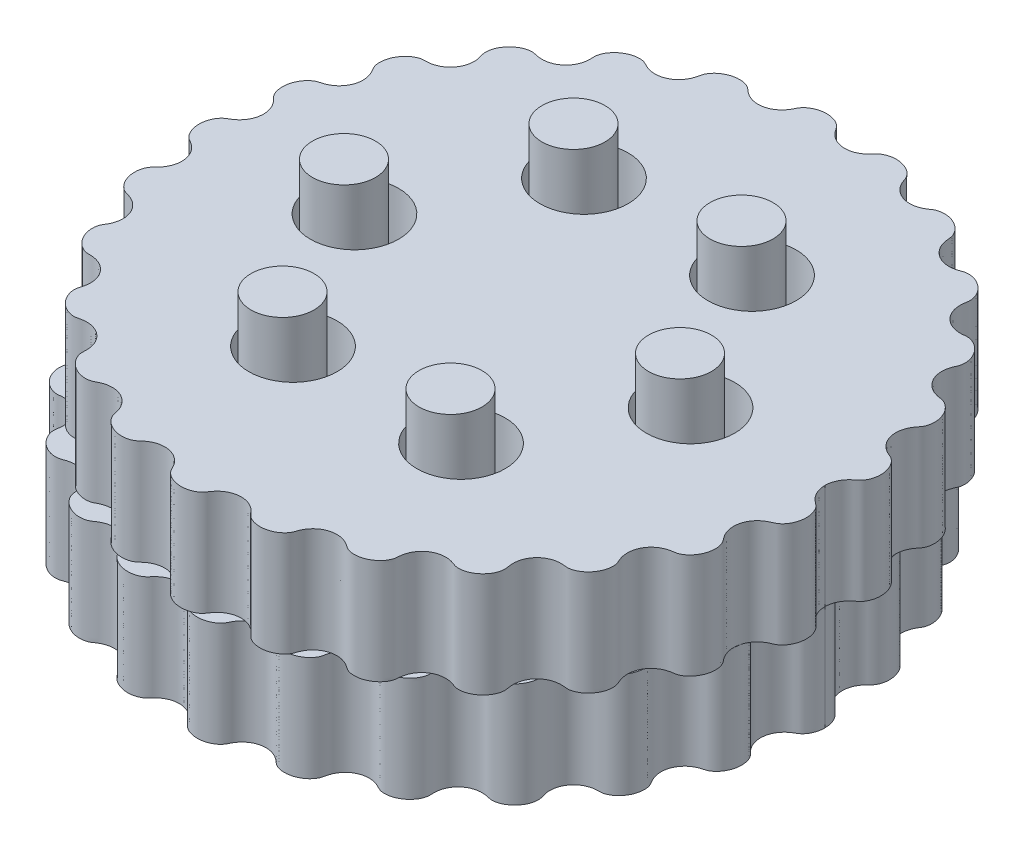
SolidWorks part; units mm, degrees
ref_plane "Front Plane" through (0, 0, 0) normal (0, 0, 1) x (1, 0, 0)
ref_plane "Top Plane" through (0, 0, 0) normal (0, 1, 0) x (1, 0, 0)
ref_plane "Right Plane" through (0, 0, 0) normal (1, 0, 0) x (0, 0, -1)
sketch "Sketch1" plane through (0, 0, 0) normal (0, 1, 0) x (1, 0, 0)
  line L0 (-15.4, 0) -> (14.4, 0) construction
  line L1 (0, 0) -> (0, -14.9128) construction
  line L2 (0, 0) -> (0, 14.9128) construction
  line L3 (-0.5, 0) -> (-0.5, -14.9128) construction
  line L4 (-0.5, 0) -> (-0.5, 14.9128) construction
  line L5 (14.4, 0) -> (15.5, 0) construction
  line L6 (0, 14.9128) -> (0, -14.9128) construction
  line L7 (5.9, 0) -> (9.1, 0) construction
  line L8 (5.9, 0) -> (7.5, 0)
  circle A0 centre (-0.5, 0) radius 16 construction
  circle A1 centre (15.5, 0) radius 1 construction
  circle A2 centre (15.0351, -3.8291) radius 1 construction
  circle A3 centre (13.6673, -7.4356) radius 1 construction
  circle A4 centre (11.4762, -10.61) radius 1 construction
  circle A5 centre (8.589, -13.1677) radius 1 construction
  circle A6 centre (5.1737, -14.9603) radius 1 construction
  circle A7 centre (1.4286, -15.8833) radius 1 construction
  circle A8 centre (-2.4286, -15.8833) radius 1 construction
  circle A9 centre (-6.1737, -14.9603) radius 1 construction
  circle A10 centre (-9.589, -13.1677) radius 1 construction
  circle A11 centre (-12.4762, -10.61) radius 1 construction
  circle A12 centre (-14.6673, -7.4356) radius 1 construction
  circle A13 centre (-16.0351, -3.8291) radius 1 construction
  circle A14 centre (-16.5, 0) radius 1 construction
  circle A15 centre (-16.0351, 3.8291) radius 1 construction
  circle A16 centre (-14.6673, 7.4356) radius 1 construction
  circle A17 centre (-12.4762, 10.61) radius 1 construction
  circle A18 centre (-9.589, 13.1677) radius 1 construction
  circle A19 centre (-6.1737, 14.9603) radius 1 construction
  circle A20 centre (-2.4286, 15.8833) radius 1 construction
  circle A21 centre (1.4286, 15.8833) radius 1 construction
  circle A22 centre (5.1737, 14.9603) radius 1 construction
  circle A23 centre (8.589, 13.1677) radius 1 construction
  circle A24 centre (11.4762, 10.61) radius 1 construction
  circle A25 centre (13.6673, 7.4356) radius 1 construction
  circle A26 centre (15.0351, 3.8291) radius 1 construction
  circle A27 centre (0, 0) radius 8
  circle A28 centre (8, 0) radius 2.1
  circle A29 centre (4, 6.9282) radius 2.1
  circle A30 centre (-4, 6.9282) radius 2.1
  circle A31 centre (-8, 0) radius 2.1
  circle A32 centre (-4, -6.9282) radius 2.1
  circle A33 centre (4, -6.9282) radius 2.1
  circle A34 centre (-1, 0) radius 8 construction
  circle A35 centre (3, -6.9282) radius 2.1
  circle A36 centre (-5, -6.9282) radius 2.1
  circle A37 centre (-9, 0) radius 2.1
  circle A38 centre (-5, 6.9282) radius 2.1
  circle A39 centre (3, 6.9282) radius 2.1
  circle A40 centre (7, 0) radius 2.1
  circle A41 centre (7.5, 0) radius 1.5
  circle A42 centre (3.5, -6.9282) radius 1.5
  circle A43 centre (-4.5, -6.9282) radius 1.5
  circle A44 centre (-8.5, 0) radius 1.5
  circle A45 centre (-4.5, 6.9282) radius 1.5
  circle A46 centre (3.5, 6.9282) radius 1.5
  spline S0 degree 4 number of poles 369 (14.1521, 3.1658) -> (-14.9531, 3.4358) construction
  spline S1 degree 4 number of poles 315 (14.4, 0) -> (-15.4, 0)
  spline S2 degree 4 number of poles 315 (14.4, 0) -> (-15.4, 0)
  spline S3 degree 4 number of poles 315 (-15.4, 0) -> (14.4, 0)
  spline S4 degree 4 number of poles 315 (-15.4, 0) -> (14.4, 0)
  point P80 (0, 0)
  dimension "D2" = 26
  dimension "D3" = 16
  dimension "D4" = 4.2
  dimension "D6" = 6
  dimension "D1" = 0.5
  dimension "D5" = 6
extrude "Rotor1" add sketch "Sketch1" along normal blind 5 contours S2 S1
sketch "Sketch3" plane through (0, 0, 0) normal (0, 1, 0) x (1, 0, 0)
  spline S0 degree 4 number of poles 315 (-15.4, 0) -> (14.4, 0)
  spline S1 degree 4 number of poles 315 (-15.4, 0) -> (14.4, 0)
extrude "Rotor2" add sketch "Sketch3" against normal blind 5
sketch "Sketch5" plane through (0, 0, 0) normal (0, 1, 0) x (1, 0, 0)
  circle A0 centre (8, 0) radius 2.1
  circle A1 centre (4, 6.9282) radius 2.1
  circle A2 centre (-4, 6.9282) radius 2.1
  circle A3 centre (-8, 0) radius 2.1
  circle A4 centre (-4, -6.9282) radius 2.1
  circle A5 centre (4, -6.9282) radius 2.1
extrude "Cut-Extrude1" cut sketch "Sketch5" along normal through all
sketch "Sketch7" plane through (0, 0, 0) normal (0, 1, 0) x (1, 0, 0)
  circle A0 centre (3, -6.9282) radius 2.1
  circle A1 centre (-5, -6.9282) radius 2.1
  circle A2 centre (-9, 0) radius 2.1
  circle A3 centre (-5, 6.9282) radius 2.1
  circle A4 centre (3, 6.9282) radius 2.1
  circle A5 centre (7, 0) radius 2.1
extrude "Cut-Extrude2" cut sketch "Sketch7" against normal through all
sketch "Sketch8" plane through (0, 0, 0) normal (0, 1, 0) x (1, 0, 0)
  circle A0 centre (7.5, 0) radius 1.5
  circle A1 centre (3.5, -6.9282) radius 1.5
  circle A2 centre (-4.5, -6.9282) radius 1.5
  circle A3 centre (-8.5, 0) radius 1.5
  circle A4 centre (-4.5, 6.9282) radius 1.5
  circle A5 centre (3.5, 6.9282) radius 1.5
extrude "Boss-Extrude3" add sketch "Sketch8" along normal blind 7 and the other way blind 7 separate body
